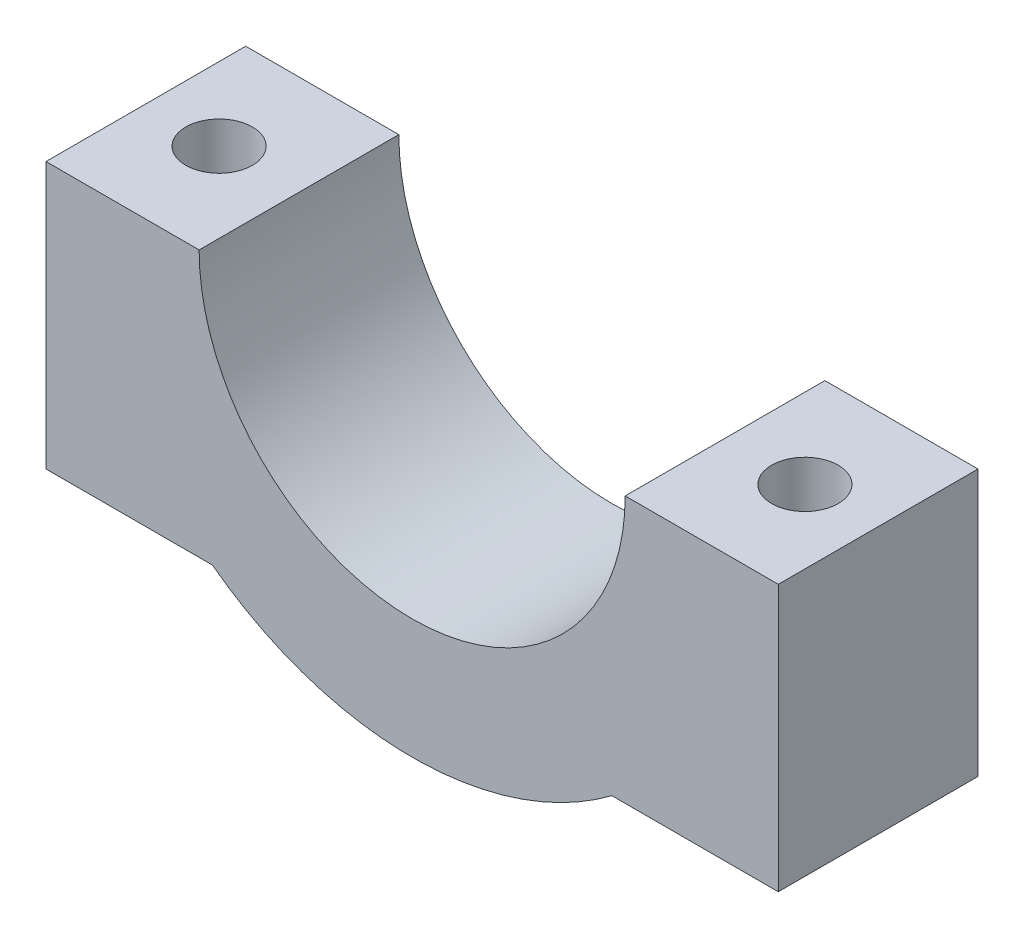
SolidWorks part; units mm, degrees
material "TIMETAL 35A CP Titanium (ASTM Grade 1) 99.1 Ti"
ref_plane "Front Plane" through (0, 0, 0) normal (0, 0, 1) x (1, 0, 0)
ref_plane "Top Plane" through (0, 0, 0) normal (0, 1, 0) x (1, 0, 0)
ref_plane "Right Plane" through (0, 0, 0) normal (1, 0, 0) x (0, 0, -1)
sketch "Sketch1" plane through (0, 0, 0) normal (0, 0, 1) x (1, 0, 0)
  line L1 (-27.5, 0) -> (-16, 0)
  line L6 (27.5, 0) -> (16, 0)
  line L7 (27.5, -20) -> (27.5, 0)
  line L8 (27.5, -20) -> (15, -20)
  line L9 (-15, -20) -> (-27.5, -20)
  line L10 (-27.5, -20) -> (-27.5, 0)
  arc A2 (16, 0) -> (-16, 0) centre (0, 0) cw
  arc A3 (15, -20) -> (-15, -20) centre (0, 0) cw
  point P1 (0, 0)
  point P2 (0, 0)
  point P4 (0, 0)
  point P5 (0, 0)
  point P6 (0, 0)
  point P8 (0, 0)
  point P9 (0, 0)
  point P11 (0, 0)
  point P12 (0, 0)
  point P13 (0, 0)
  point P19 (0, 0)
  point P20 (0, 0)
  point P21 (0, 0)
  dimension "D2" = 25
  dimension "D3" = 16
  dimension "D4" = 11.5
  dimension "D1" = 20
extrude "Boss-Extrude1" add sketch "Sketch1" along normal blind 7.5 and the other way blind 7.5
sketch "Sketch2" plane through (0, -20, 0) normal (0, 1, 0) x (-1, 0, 0)
  circle A0 centre (-22, 0) radius 3
  circle A1 centre (22, 0) radius 3
  point P4 (21.0132, 1.02)
  point P6 (0, 0)
  point P7 (0, 0)
  dimension "D1" = 6
  dimension "D3" = 22
  dimension "D2" = 44
hole_wizard "Tap Drill for M6 Tap1" positions "Sketch3" profile "Sketch4" hole size "M6" standard "ISO" end condition through all
sketch "Sketch3" plane through (0, -20, 0) normal (0, -1, 0) x (-1, 0, 0)
  point P0 (22, 0)
  point P3 (-22, 0)
sketch "Sketch4" plane through (-22, -20, 0) normal (1, 0, 0) x (0, 0, -1)
  line L0 (0, 0) -> (0, 20)
  line L1 (0, 20) -> (2.5, 20)
  line L2 (2.5, 20) -> (2.5, 0)
  line L5 (2.5, 0) -> (0, 0)
  line L11 (0, -6.35) -> (0, 107.95) construction
  dimension "Thru Hole Dia." = 5
  dimension "Thru Hole Depth" = 20
